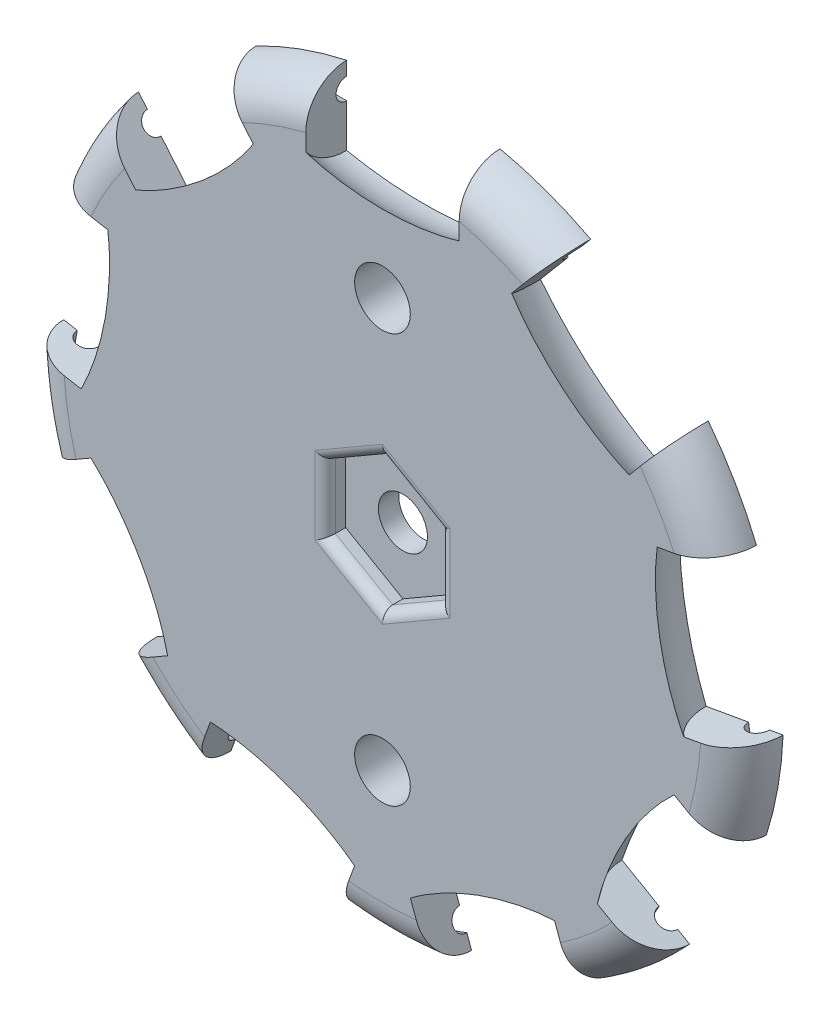
SolidWorks part; units mm, degrees
ref_plane "Front Plane" through (0, 0, 0) normal (0, 0, 1) x (1, 0, 0)
ref_plane "Top Plane" through (0, 0, 0) normal (0, 1, 0) x (1, 0, 0)
ref_plane "Right Plane" through (0, 0, 0) normal (1, 0, 0) x (0, 0, -1)
sketch "Sketch1" plane through (0, 0, 0) normal (0, 0, 1) x (1, 0, 0)
  circle A0 centre (0, 0) radius 27.94
  dimension "D1" = 55.88
extrude "Boss-Extrude1" add sketch "Sketch1" along normal blind 3.175
fillet "Fillet1" radius 3.1852 1 edges at (27.94, 0, 3.175)
sketch "Sketch2" plane through (0, 0, 3.175) normal (0, 0, 1) x (1, 0, 0)
  line L0 (0, -15.875) -> (0, 15.875) construction
  line L1 (0, 0) -> (0, 6.4682) construction
  circle A0 centre (0, 15.875) radius 2.159
  circle A1 centre (0, -15.875) radius 2.159
  circle A4 centre (0, 0) radius 1.905
  point P9 (0, 0)
  dimension "D2" = 4.318
  dimension "D4" = 3.81
  dimension "D1" = 15.875
  dimension "D3" = 2
extrude "Cut-Extrude1" cut sketch "Sketch2" against normal through all
sketch "Sketch5" plane through (0, 0, 0) normal (0, 0, 1) x (1, 0, 0)
  line L0 (-5.9531, 25.4) -> (5.9531, 25.4)
  line L1 (5.9531, 25.4) -> (5.9531, 29.5692)
  line L2 (-5.9531, 25.4) -> (-5.9531, 29.5692)
  line L3 (-5.9531, 25.4) -> (-8.5086, 25.4) construction
  arc A0 (-5.9531, 29.5692) -> (5.9531, 29.5692) centre (0, 0) cw
  circle A1 centre (0, 0) radius 27.94 construction
  point P5 (0, 25.4)
  point P9 (0, 30.1625)
  dimension "D1" = 11.9062
  dimension "D2" = 25.4
  dimension "D3" = 9.525
revolve "Cut-Revolve1" cut sketch "Sketch5" angle 360 about L3
sketch "Sketch6" plane through (0, 0, 0) normal (1, 0, 0) x (0, 0, -1)
  line L0 (0, -27.94) -> (0, 27.2984) construction
  circle A0 centre (0, 25.4) radius 0.8255
  arc A1 (-3.175, 22.6979) -> (0, 21.2308) centre (0, 25.4) ccw construction
  dimension "D1" = 1.651
extrude "Cut-Extrude2" cut sketch "Sketch6" against normal mid plane 15.875
pattern_circular "CirPattern1" count 9 over 360 about axis through (0, 0, 0) along (0, 0, 1) of "Cut-Revolve1", "Cut-Extrude2"
sketch "Sketch8" plane through (0, 0, 3.175) normal (0, 0, 1) x (1, 0, 0)
  line L1 (0, 5.1326) -> (-4.445, 2.5663)
  line L2 (-4.445, 2.5663) -> (-4.445, -2.5663)
  line L3 (-4.445, -2.5663) -> (0, -5.1326)
  line L4 (0, -5.1326) -> (4.445, -2.5663)
  line L5 (4.445, -2.5663) -> (4.445, 2.5663)
  line L6 (4.445, 2.5663) -> (0, 5.1326)
  circle A0 centre (0, 0) radius 4.445 construction
  dimension "D1" = 8.89
extrude "Cut-Extrude4" cut sketch "Sketch8" against normal blind 1.5875
fillet "Fillet2" radius 0.7937 6 edges at (-2.2225, 3.8495, 3.175) (-4.445, 0, 3.175) (-2.2225, -3.8495, 3.175) (2.2225, -3.8495, 3.175) (4.445, 0, 3.175) (2.2225, 3.8495, 3.175)
